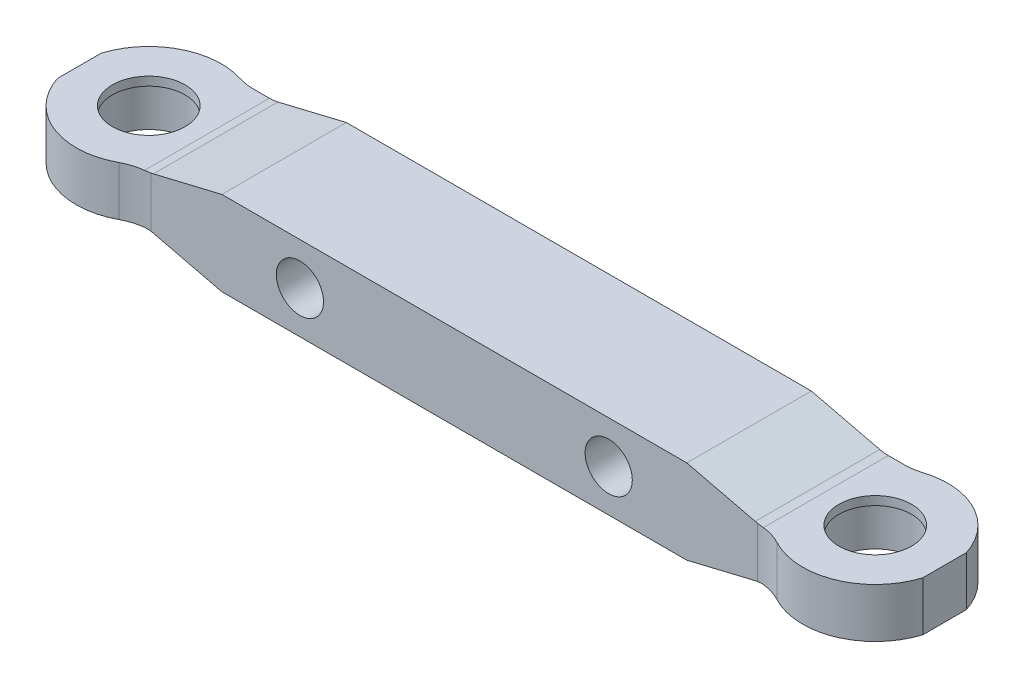
SolidWorks part; units mm, degrees
ref_plane "Front Plane" through (0, 0, 0) normal (0, 0, 1) x (1, 0, 0)
ref_plane "Top Plane" through (0, 0, 0) normal (0, 1, 0) x (1, 0, 0)
ref_plane "Right Plane" through (0, 0, 0) normal (1, 0, 0) x (0, 0, -1)
sketch "Sketch2" plane through (0, 0, 0) normal (0, 1, 0) x (1, 0, 0)
  line L0 (0, 0.003) -> (0, 0.0871) construction
  line L1 (-58.5226, 21.7678) -> (58.5226, 21.7678)
  line L2 (-55.7794, 0) -> (55.7794, 0)
  line L3 (-75.615, 6.2738) -> (-75.615, 13.8938)
  line L4 (75.615, 6.2738) -> (75.615, 13.8938)
  circle A0 centre (-63.5, 10.0838) radius 7.1247
  circle A1 centre (63.5, 10.0838) radius 7.1247
  arc A2 (-58.5226, 21.7678) -> (-75.615, 13.8938) centre (-63.5, 10.0838) ccw
  arc A3 (55.7794, 0) -> (75.615, 6.2738) centre (63.5, 10.0838) ccw
  arc A4 (75.615, 13.8938) -> (58.5226, 21.7678) centre (63.5, 10.0838) ccw
  arc A5 (-75.615, 6.2738) -> (-55.7794, 0) centre (-63.5, 10.0838) ccw
  point P12 (-63.5, 22.7838)
  dimension "D3" = 14.2494
  dimension "D4" = 25.4
  dimension "D1" = 21.7678
  dimension "D2" = 127
  dimension "D5" = 1.016
  dimension "D6" = 7.62
extrude "Boss-Extrude1" add sketch "Sketch2" along normal blind 14.732
sketch "Sketch3" plane through (0, 0, -21.7678) normal (0, 0, -1) x (-1, 0, 0)
  line L0 (58.5226, 7.366) -> (34.4386, 7.366) construction
  line L2 (-58.5226, 14.732) -> (-58.5226, 0) construction
  line L3 (-58.5226, 14.732) -> (-58.5226, 0) construction
  line L4 (53.34, 7.366) -> (53.34, -14.3235) construction
  line L5 (40.64, 7.366) -> (40.64, -14.3235) construction
  line L6 (-58.5226, 0) -> (58.5226, 0) construction
  line L8 (0, 0) -> (0, -12.3509) construction
  line L9 (53.34, 3.048) -> (78.74, 3.048)
  line L10 (40.64, 0) -> (53.34, 3.048)
  line L11 (40.64, 0) -> (40.64, -5.08)
  line L12 (40.64, -5.08) -> (78.74, -5.08)
  line L13 (78.74, -5.08) -> (78.74, 3.048)
  line L14 (40.64, 14.732) -> (40.64, 19.812)
  line L15 (40.64, 14.732) -> (53.34, 11.684)
  line L16 (53.34, 11.684) -> (78.74, 11.684)
  line L17 (78.74, 19.812) -> (78.74, 11.684)
  line L18 (40.64, 19.812) -> (78.74, 19.812)
  line L19 (-78.74, -5.08) -> (-78.74, 3.048)
  line L20 (-53.34, 3.048) -> (-78.74, 3.048)
  line L21 (-40.64, 0) -> (-53.34, 3.048)
  line L22 (-40.64, -5.08) -> (-78.74, -5.08)
  line L23 (-40.64, 0) -> (-40.64, -5.08)
  line L24 (-40.64, 14.732) -> (-40.64, 19.812)
  line L25 (-40.64, 14.732) -> (-53.34, 11.684)
  line L26 (-40.64, 19.812) -> (-78.74, 19.812)
  line L27 (-78.74, 19.812) -> (-78.74, 11.684)
  line L28 (-53.34, 11.684) -> (-78.74, 11.684)
  circle A0 centre (26.9875, 7.366) radius 2.3622
  circle A1 centre (-26.9875, 7.366) radius 2.3622
  point P3 (-58.5226, 7.366)
  point P6 (0, 0)
  dimension "D3" = 4.7244
  dimension "D1" = 40.64
  dimension "D2" = 53.34
  dimension "D4" = 53.975
  dimension "D5" = 4.318
  dimension "D6" = 5.08
  dimension "D7" = 38.1
extrude "Cut-Extrude1" cut sketch "Sketch3" against normal through all both and the other way through all
sketch "Sketch4" plane through (0, 0, 0) normal (0, 0, 1) x (1, 0, 0)
  circle A0 centre (-26.9875, 7.366) radius 4.1275
  circle A1 centre (26.9875, 7.366) radius 4.1275
  dimension "D1" = 8.255
extrude "Cut-Extrude2" cut sketch "Sketch4" against normal blind 8.89
fillet "Fillet2" radius 9.525 4 edges at (-58.5226, 7.366, -21.7678) (58.5226, 7.366, -21.7678) (55.7794, 7.366, 0) (-55.7794, 7.366, 0)
fillet "Fillet3" radius 6.35 4 edges at (53.34, 11.684, -10.8815) (-53.34, 11.684, -10.8815) (-53.34, 3.048, -10.8815) (53.34, 3.048, -10.8815)
sketch "Sketch5" plane through (0, 11.684, 0) normal (0, 1, 0) x (1, 0, 0)
  circle A0 centre (63.5, 10.0838) radius 7.1247 construction
  circle A1 centre (-63.5, 10.0838) radius 7.1247 construction
  circle A2 centre (63.5, 10.0838) radius 7.1247
  circle A3 centre (-63.5, 10.0838) radius 7.1247
  circle A4 centre (63.5, 10.0838) radius 6.35
  circle A5 centre (-63.5, 10.0838) radius 6.35
  dimension "D1" = 12.7
extrude "Boss-Extrude2" add sketch "Sketch5" against normal blind 1.524
